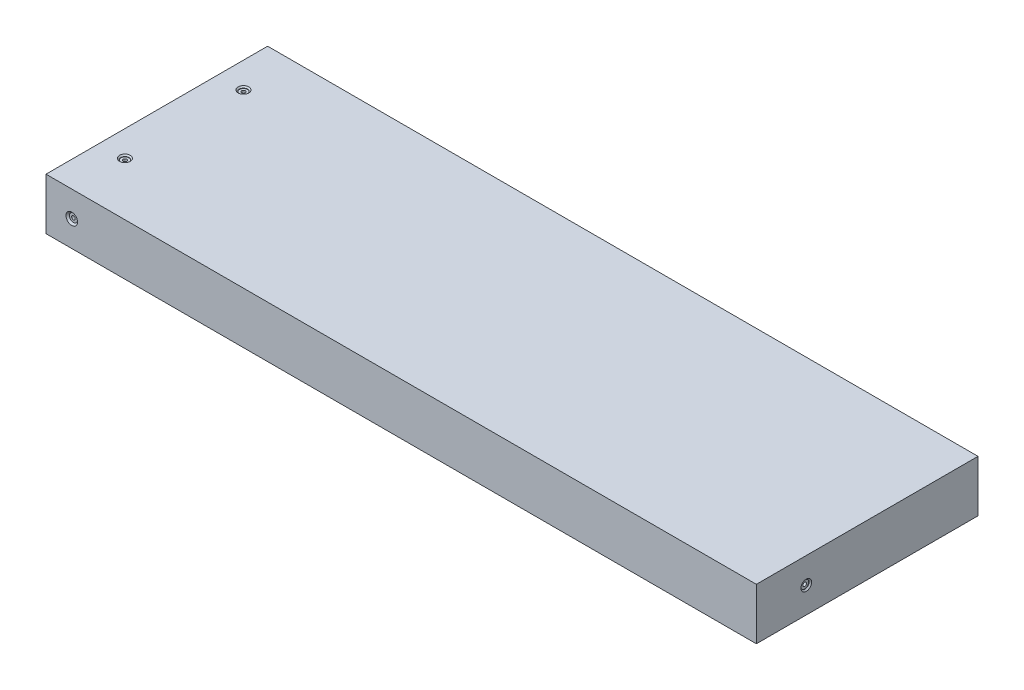
SolidWorks part; units mm, degrees
ref_plane "Front Plane" through (0, 0, 0) normal (0, 0, 1) x (1, 0, 0)
ref_plane "Top Plane" through (0, 0, 0) normal (0, 1, 0) x (1, 0, 0)
ref_plane "Right Plane" through (0, 0, 0) normal (1, 0, 0) x (0, 0, -1)
sketch "Sketch1" plane through (0, 0, 0) normal (0, 1, 0) x (1, 0, 0)
  line L1 (-175, 54.6) -> (175, 54.6)
  line L2 (-175, 54.6) -> (-175, -54.6)
  line L3 (-175, -54.6) -> (175, -54.6)
  line L4 (175, 54.6) -> (175, -54.6)
  line L5 (-175, 54.6) -> (175, -54.6) construction
  line L6 (-175, -54.6) -> (175, 54.6) construction
  point P0 (0, 0)
  dimension "D1" = 109.2
  dimension "D2" = 350
extrude "Boss-Extrude1" add sketch "Sketch1" along normal blind 25.4
hole_wizard "CBORE for #0 Binding Head Machine Screw1" positions "Sketch2" profile "Sketch3" counterbore size "#0" standard "ANSI Inch"
sketch "Sketch2" plane through (0, 0, 54.6) normal (0, 0, 1) x (1, 0, 0)
  line L0 (-175, 25.4) -> (-175, 0) construction
  line L1 (-175, 25.4) -> (175, 25.4) construction
  point P0 (-162.3, 12.7)
  dimension "D1" = 12.7
  dimension "D2" = 12.7
sketch "Sketch3" plane through (-162.3, 12.7, 54.6) normal (1, 0, 0) x (0, -1, 0)
  line L0 (0, 0) -> (0, 30.5342)
  line L1 (0, 30.5342) -> (0.889, 30)
  line L2 (0.889, 30) -> (0.889, 0.8128)
  line L3 (0.889, 0.8128) -> (1.985, 0.8128)
  line L5 (1.985, 0.8128) -> (1.985, 0.8725)
  line L6 (1.985, 0.8725) -> (2.8575, 0)
  line L7 (2.8575, 0) -> (0, 0)
  line L8 (-1.985, 0.8725) -> (-2.8575, 0) construction
  line L10 (0, 30.5342) -> (-0.889, 30) construction
  line L11 (0, -6.35) -> (0, 107.95) construction
  dimension "Hole Dia." = 1.778
  dimension "Hole Depth" = 30
  dimension "C'Bore Dia." = 3.97
  dimension "C'Bore Depth" = 0.8128
  dimension "Near C'Sink Dia." = 5.715
  dimension "Near C'Sink Angle" = 90
  dimension "Drill Angle" = 118
mirror "Mirror1" about plane through (0, 0, 0) normal (0, 0, 1) of "CBORE for #0 Binding Head Machine Screw1"
hole_wizard "CBORE for #0 Binding Head Machine Screw2" positions "Sketch4" profile "Sketch5" counterbore size "#0" standard "ANSI Inch"
sketch "Sketch4" plane through (175, 0, 0) normal (1, 0, 0) x (0, 0, -1)
  line L0 (-54.6, 25.4) -> (-54.6, 0) construction
  line L2 (-54.6, 25.4) -> (54.6, 25.4) construction
  point P0 (-30, -45.7)
  point P2 (-30, 12.7)
  dimension "D1" = 58.4
  dimension "D2" = 24.6
  dimension "D4" = 12.7
sketch "Sketch5" plane through (175, -45.7, 30) normal (0, 1, 0) x (0, 0, -1)
  line L0 (0, 0) -> (0, 30.5342)
  line L1 (0, 30.5342) -> (0.889, 30)
  line L2 (0.889, 30) -> (0.889, 0.8128)
  line L3 (0.889, 0.8128) -> (1.985, 0.8128)
  line L5 (1.985, 0.8128) -> (1.985, 0.635)
  line L6 (1.985, 0.635) -> (2.62, 0)
  line L7 (2.62, 0) -> (0, 0)
  line L8 (-1.985, 0.635) -> (-2.62, 0) construction
  line L10 (0, 30.5342) -> (-0.889, 30) construction
  line L11 (0, -6.35) -> (0, 107.95) construction
  dimension "Hole Dia." = 1.778
  dimension "Hole Depth" = 30
  dimension "C'Bore Dia." = 3.97
  dimension "C'Bore Depth" = 0.8128
  dimension "Near C'Sink Dia." = 5.24
  dimension "Near C'Sink Angle" = 90
  dimension "Drill Angle" = 118
hole_wizard "CBORE for #0 Binding Head Machine Screw3" positions "Sketch6" profile "Sketch7" counterbore size "#0" standard "ANSI Inch"
sketch "Sketch6" plane through (0, 25.4, 0) normal (0, 1, 0) x (1, 0, 0)
  line L0 (-175, 54.6) -> (-175, -54.6) construction
  line L1 (175, 54.6) -> (-175, 54.6) construction
  point P0 (-162.3, 30)
  point P2 (-162.3, -28.4)
  dimension "D1" = 12.7
  dimension "D2" = 58.4
  dimension "D3" = 24.6
  dimension "D4" = 12.7
sketch "Sketch7" plane through (-162.3, 25.4, -30) normal (1, 0, 0) x (0, 0, 1)
  line L0 (0, 0) -> (0, 30.5342)
  line L1 (0, 30.5342) -> (0.889, 30)
  line L2 (0.889, 30) -> (0.889, 0.8128)
  line L3 (0.889, 0.8128) -> (1.985, 0.8128)
  line L5 (1.985, 0.8128) -> (1.985, 0.635)
  line L6 (1.985, 0.635) -> (2.62, 0)
  line L7 (2.62, 0) -> (0, 0)
  line L8 (-1.985, 0.635) -> (-2.62, 0) construction
  line L10 (0, 30.5342) -> (-0.889, 30) construction
  line L11 (0, -6.35) -> (0, 107.95) construction
  dimension "Hole Dia." = 1.778
  dimension "Hole Depth" = 30
  dimension "C'Bore Dia." = 3.97
  dimension "C'Bore Depth" = 0.8128
  dimension "Near C'Sink Dia." = 5.24
  dimension "Near C'Sink Angle" = 90
  dimension "Drill Angle" = 118
